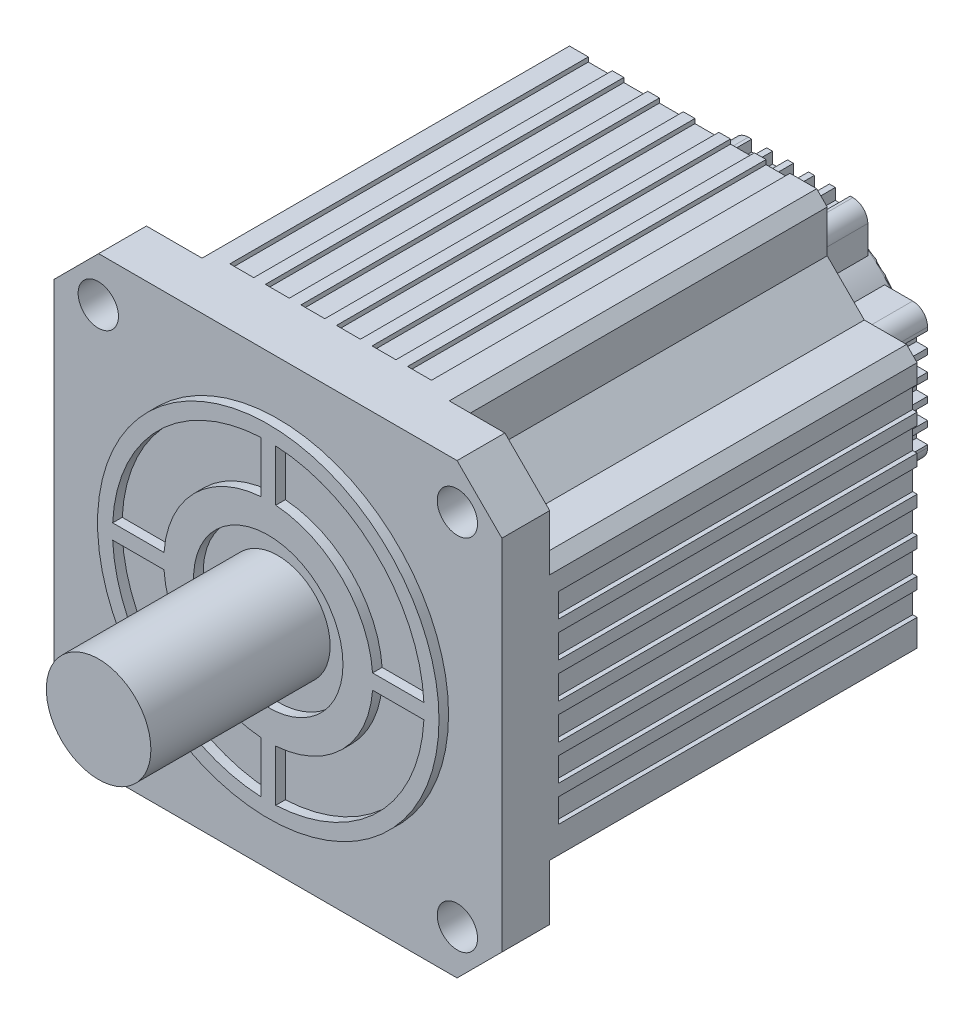
SolidWorks part; units mm, degrees
note: The reader was unsure of these and kept them because the rebuilt part matched: shared geometry of "草图16<3>".
ref_plane "前视基准面" through (0, 0, 0) normal (0, 0, 1) x (1, 0, 0)
ref_plane "上视基准面" through (0, 0, 0) normal (0, 1, 0) x (1, 0, 0)
ref_plane "右视基准面" through (0, 0, 0) normal (1, 0, 0) x (0, 0, -1)
sketch "草图1" plane through (0, 0, 0) normal (0, 0, 1) x (1, 0, 0)
  line L0 (-60, 75) -> (-75, 60)
  line L1 (-60, 75) -> (60, 75)
  line L2 (-75, 60) -> (-75, -60)
  line L3 (-60, -75) -> (60, -75)
  line L4 (75, 60) -> (75, -60)
  line L5 (-75, 75) -> (75, -75) construction
  line L6 (-75, -75) -> (75, 75) construction
  line L7 (60, 75) -> (75, 60)
  line L8 (75, -60) -> (60, -75)
  line L9 (-75, -60) -> (-60, -75)
  point P0 (0, 0)
  dimension "D1" = 150
  dimension "D2" = 150
extrude "拉伸1" add sketch "草图1" along normal blind 16
sketch "草图3" plane through (0, 0, 16) normal (0, 0, 1) x (1, 0, 0)
  line L0 (67.5, 67.5) -> (-67.5, -67.5) construction
  line L1 (75, 60) -> (60, 75) construction
  line L2 (-75, -60) -> (-60, -75) construction
  line L3 (-67.5, 67.5) -> (67.5, -67.5) construction
  line L4 (-60, 75) -> (-75, 60) construction
  line L5 (60, -75) -> (75, -60) construction
  circle A0 centre (0, 0) radius 100 construction
sketch "草图5" plane through (0, 0, 16) normal (0, 0, 1) x (1, 0, 0)
  circle A0 centre (0, 0) radius 57.15
  dimension "D1" = 114.3
extrude "拉伸2" add sketch "草图5" along normal blind 3.2
sketch "草图6" plane through (0, 0, 19.2) normal (0, 0, 1) x (1, 0, 0)
  circle A0 centre (0, 0) radius 52.15
  dimension "D1" = 104.3
extrude "拉伸3" cut sketch "草图6" against normal blind 3.2
sketch "草图7" plane through (0, 0, 16) normal (0, 0, 1) x (1, 0, 0)
  circle A0 centre (0, 0) radius 17.5
  dimension "D1" = 35
extrude "拉伸4" add sketch "草图7" along normal blind 60
sketch "草图9" plane through (0, 0, 16) normal (0, 0, 1) x (1, 0, 0)
  line L0 (0, 0) -> (102.718, 0) construction
  line L1 (25.0777, 2.5) -> (54.3657, 2.5)
  line L3 (25.0777, -2.5) -> (54.3657, -2.5)
  line L4 (54.3657, 2.5) -> (54.3657, -2.5)
  line L5 (25.0777, 2.5) -> (25.0777, -2.5)
  dimension "D1" = 2.5
  dimension "D2" = 2.5
extrude "拉伸5" add sketch "草图9" along normal blind 3.2
pattern_circular "阵列(圆周)1" count 4 over 360 about axis through (0, 0, 0) along (0, 0, 1) of "拉伸5"
sketch "草图10" plane through (0, 0, 16) normal (0, 0, 1) x (1, 0, 0)
  circle A0 centre (0, 0) radius 35
  circle A1 centre (0, 0) radius 25
extrude "拉伸6" add sketch "草图10" along normal blind 3.2
sketch "草图11" plane through (0, 0, 0) normal (0, 0, -1) x (-1, 0, 0)
  line L0 (-75, 41.3757) -> (-75, 11.8722)
  line L1 (-75, -60) -> (-75, 60) construction
  line L2 (75, 60) -> (75, -60) construction
  line L3 (11.8722, 75) -> (-41.3757, 75)
  line L4 (-60, 75) -> (60, 75) construction
  line L5 (-41.3757, 75) -> (-44.9113, 71.4645)
  line L6 (-71.4645, 44.9113) -> (-57.3223, 44.9113)
  line L7 (-57.3223, 44.9113) -> (-44.9113, 57.3223)
  line L8 (-44.9113, 57.3223) -> (-44.9113, 71.4645)
  line L9 (41.3757, 75) -> (11.8722, 75)
  line L10 (-71.4645, 44.9113) -> (-75, 41.3757)
  line L11 (44.9113, 71.4645) -> (41.3757, 75)
  line L12 (44.9113, 71.4645) -> (44.9113, 57.3223)
  line L13 (44.9113, 57.3223) -> (57.3223, 44.9113)
  line L14 (57.3223, 44.9113) -> (71.4645, 44.9113)
  line L15 (75, 41.3757) -> (71.4645, 44.9113)
  line L16 (75, -41.3757) -> (75, -11.8722)
  line L17 (71.4645, -44.9113) -> (75, -41.3757)
  line L18 (71.4645, -44.9113) -> (57.3223, -44.9113)
  line L19 (57.3223, -44.9113) -> (44.9113, -57.3223)
  line L20 (44.9113, -57.3223) -> (44.9113, -71.4645)
  line L21 (41.3757, -75) -> (44.9113, -71.4645)
  line L22 (-41.3757, -75) -> (-11.8722, -75)
  line L23 (-44.9113, -71.4645) -> (-41.3757, -75)
  line L24 (-44.9113, -71.4645) -> (-44.9113, -57.3223)
  line L25 (-44.9113, -57.3223) -> (-57.3223, -44.9113)
  line L26 (-57.3223, -44.9113) -> (-71.4645, -44.9113)
  line L29 (-75, -41.3757) -> (-71.4645, -44.9113)
  line L30 (-75, 11.8722) -> (-75, -41.3757)
  line L31 (75, 41.3757) -> (75, -11.8722)
  line L32 (-11.8722, -75) -> (41.3757, -75)
  point P2 (-75, 41.3757)
  point P7 (-71.4645, 44.9113)
  point P39 (-44.9113, 71.4645)
  point P42 (-41.3757, 75)
  dimension "D9" = 45
  dimension "D14" = 10
  dimension "D6" = 5
  dimension "D7" = 5
  dimension "D10" = 45
extrude "拉伸7" add sketch "草图11" along normal blind 123
sketch "草图12" plane through (0, 0, -123) normal (0, 0, -1) x (-1, 0, 0)
  line L0 (-42.5, -17.5) -> (-42.5, 17.5)
  line L1 (-17.5, -42.5) -> (17.5, -42.5)
  line L2 (42.5, -17.5) -> (42.5, 17.5)
  line L3 (22.5, 28.1066) -> (22.5, 37.4966)
  line L5 (-22.5, 28.1066) -> (-22.5, 37.4966)
  line L6 (-17.5, 42.4966) -> (17.5, 42.4966)
  line L10 (-28.1066, 22.5) -> (-37.5, 22.5)
  line L11 (37.5, 22.5) -> (28.1066, 22.5)
  line L12 (28.1066, -22.5) -> (37.5, -22.5)
  line L14 (22.5, -37.5) -> (22.5, -28.1066)
  line L15 (-22.5, -28.1066) -> (-22.5, -37.5)
  line L17 (-37.5, -22.5) -> (-28.1066, -22.5)
  line L23 (22.5, 28.1066) -> (22.5, 30) [skipped]
  arc A0 (-37.5, 22.5) -> (-42.5, 17.5) centre (-37.5, 17.5) ccw
  arc A1 (-17.5, 42.4966) -> (-22.5, 37.4966) centre (-17.5, 37.4966) ccw
  arc A2 (22.5, 37.4966) -> (17.5, 42.4966) centre (17.5, 37.4966) ccw
  arc A3 (42.5, 17.5) -> (37.5, 22.5) centre (37.5, 17.5) ccw
  arc A4 (37.5, -22.5) -> (42.5, -17.5) centre (37.5, -17.5) ccw
  arc A5 (17.5, -42.5) -> (22.5, -37.5) centre (17.5, -37.5) ccw
  arc A6 (-22.5, -37.5) -> (-17.5, -42.5) centre (-17.5, -37.5) ccw
  arc A7 (-42.5, -17.5) -> (-37.5, -22.5) centre (-37.5, -17.5) ccw
  arc A10 (28.1066, 22.5) -> (22.5, 28.1066) centre (0, 0) ccw
  arc A11 (22.5, -28.1066) -> (28.1066, -22.5) centre (0, 0) ccw
  arc A12 (-28.1066, -22.5) -> (-22.5, -28.1066) centre (0, 0) ccw
  arc A16 (-22.5, 28.1066) -> (-28.1066, 22.5) centre (0, 0) ccw
  point P6 (-22.5, 42.4966)
  point P11 (22.5, 42.4966)
  point P38 (-26.0355, 22.5)
  point P41 (-22.5, 26.0355)
  dimension "D1" = 5
  dimension "D2" = 14.39
  dimension "D4" = 5
  dimension "D3" = 14.39
  dimension "D8" = 5
extrude "拉伸8" add sketch "草图12" along normal blind 36
sketch "草图13" plane through (0, 0, -159) normal (0, 0, -1) x (-1, 0, 0)
  circle A0 centre (0, 0) radius 36.0032
extrude "拉伸9" add sketch "草图13" along normal blind 2
fillet "圆角5" radius 1 1 edges at (-36.0032, 0, -161)
sketch "草图14" plane through (0, 0, -123) normal (0, 0, -1) x (-1, 0, 0)
  line L0 (-32.4376, 73.5025) -> (-24.4376, 73.5025)
  line L2 (-24.4376, 73.5025) -> (-24.4376, 87.3537)
  line L3 (-24.4376, 87.3537) -> (-32.4376, 87.3537)
  line L5 (-32.4376, 87.3537) -> (-32.4376, 73.5025)
extrude "拉伸10" cut sketch "草图14" against normal blind 120
sketch "草图15" plane through (0, 0, -159) normal (0, 0, -1) x (-1, 0, 0)
  line L0 (-16.3794, -43.7336) -> (-16.3794, -38.7472)
  line L1 (-16.3794, -38.7472) -> (-11.3794, -38.7472)
  line L2 (-11.3794, -38.7472) -> (-11.3794, -43.7336)
  line L3 (-11.3794, -43.7336) -> (-16.3794, -43.7336)
  dimension "D1" = 5
extrude "拉伸11" cut sketch "草图15" against normal blind 44
pattern_linear "阵列(线性)4" count 5 spacing 7 along (-1, 0, 0) of "拉伸11"
sketch "草图16" plane through (0, 0, -161) normal (0, 0, -1) x (-1, 0, 0)
  line L0 (3.7784, 12.9251) -> (-4.4895, 12.9251)
  line L1 (-5.3556, 11.4251) -> (-2.0876, 5.7648)
  line L2 (-0.3556, 5.7648) -> (2.9124, 11.4251)
  line L3 (3.7784, 12.9251) -> (13.498, 12.9251)
  line L4 (3.7784, 13.9251) -> (13.2661, 13.9251)
  line L5 (-2.0876, 20.0854) -> (-10.3556, 5.7648)
  line L6 (-9.4895, 4.2648) -> (7.0464, 4.2648)
  line L7 (7.9124, 5.7648) -> (4.6444, 11.4251)
  line L8 (3.7784, 13.9251) -> (13.498, 13.9251) construction
  line L9 (2.9124, 14.4251) -> (-0.3556, 20.0854)
  line L10 (-6.7983, -9.8656) -> (-14.7983, -9.8656)
  line L11 (-15.7983, -10.8656) -> (-15.7983, -14.8656)
  line L12 (-14.7983, -15.8656) -> (-6.7983, -15.8656)
  line L13 (-6.7983, -15.8656) -> (-6.7983, -11.7903)
  line L14 (-6.7983, -11.7903) -> (-10.7983, -11.7903)
  line L15 (-10.7983, -11.7903) -> (-10.7983, -12.8656)
  line L16 (-10.7983, -12.8656) -> (-10.0983, -12.8656)
  line L17 (-9.7983, -13.1656) -> (-9.7983, -14.5656)
  line L18 (-10.0983, -14.8656) -> (-12.7983, -14.8656)
  line L19 (-12.7983, -14.8656) -> (-12.7983, -10.8656)
  line L20 (-12.7983, -10.8656) -> (-6.7983, -10.8656)
  line L21 (-6.7983, -10.8656) -> (-6.7983, -9.8656)
  line L22 (3.7341, -9.8656) -> (-4.2659, -9.8656)
  line L23 (-5.2659, -10.8656) -> (-5.2659, -12.8656)
  line L24 (-4.2659, -13.8656) -> (0.4341, -13.8656)
  line L25 (0.7341, -14.1656) -> (0.7341, -14.4491)
  line L26 (-5.2659, -14.7491) -> (0.4341, -14.7491)
  line L27 (-5.2659, -14.7491) -> (-5.2659, -15.8656)
  line L28 (-5.2659, -15.8656) -> (2.7341, -15.8656)
  line L29 (3.7341, -14.8656) -> (3.7341, -12.8656)
  line L30 (2.7341, -11.8656) -> (-1.9659, -11.8656)
  line L31 (-2.2659, -11.5656) -> (-2.2659, -11.1656)
  line L32 (-1.9659, -10.8656) -> (3.7341, -10.8656)
  line L33 (6.1202, -9.8656) -> (6.1202, -15.8656)
  line L34 (6.1202, -15.8656) -> (9.1202, -15.8656)
  line L35 (9.1202, -15.8656) -> (9.1202, -14.3656)
  line L36 (9.1202, -14.3656) -> (11.6916, -15.8656)
  line L37 (11.6916, -15.8656) -> (15.1202, -15.8656)
  line L38 (15.1202, -15.8656) -> (9.1202, -12.3656)
  line L39 (9.1202, -12.3656) -> (9.1202, -9.8656)
  line L40 (9.1202, -9.8656) -> (6.1202, -9.8656)
  line L41 (3.7341, -10.8656) -> (3.7341, -9.8656)
  circle A0 centre (-1.2216, 10.0383) radius 15
  arc A1 (3.7784, 13.9251) -> (2.9124, 14.4251) centre (3.7784, 14.9251) cw
  arc A2 (-0.3556, 20.0854) -> (-2.0876, 20.0854) centre (-1.2216, 19.5854) ccw
  arc A3 (-5.3556, 11.4251) -> (-4.4895, 12.9251) centre (-4.4895, 11.9251) cw
  arc A4 (-9.4895, 4.2648) -> (-10.3556, 5.7648) centre (-9.4895, 5.2648) cw
  arc A5 (7.9124, 5.7648) -> (7.0464, 4.2648) centre (7.0464, 5.2648) cw
  arc A6 (2.9124, 11.4251) -> (4.6444, 11.4251) centre (3.7784, 10.9251) cw
  arc A7 (-2.0876, 5.7648) -> (-0.3556, 5.7648) centre (-1.2216, 6.2648) ccw
  circle A8 centre (12.2447, -11.202) radius 1.5
  arc A9 (-14.7983, -15.8656) -> (-15.7983, -14.8656) centre (-14.7983, -14.8656) cw
  arc A10 (-14.7983, -9.8656) -> (-15.7983, -10.8656) centre (-14.7983, -10.8656) ccw
  arc A11 (-5.2659, -10.8656) -> (-4.2659, -9.8656) centre (-4.2659, -10.8656) cw
  arc A12 (-4.2659, -13.8656) -> (-5.2659, -12.8656) centre (-4.2659, -12.8656) cw
  arc A13 (3.7341, -12.8656) -> (2.7341, -11.8656) centre (2.7341, -12.8656) ccw
  arc A14 (2.7341, -15.8656) -> (3.7341, -14.8656) centre (2.7341, -14.8656) ccw
  arc A15 (-1.9659, -10.8656) -> (-2.2659, -11.1656) centre (-1.9659, -11.1656) ccw
  arc A16 (-1.9659, -11.8656) -> (-2.2659, -11.5656) centre (-1.9659, -11.5656) cw
  arc A17 (0.7341, -14.1656) -> (0.4341, -13.8656) centre (0.4341, -14.1656) ccw
  arc A18 (0.4341, -14.7491) -> (0.7341, -14.4491) centre (0.4341, -14.4491) ccw
  arc A19 (-9.7983, -13.1656) -> (-10.0983, -12.8656) centre (-10.0983, -13.1656) ccw
  arc A20 (-9.7983, -14.5656) -> (-10.0983, -14.8656) centre (-10.0983, -14.5656) cw
  point P3 (-1.2216, 10.0383)
  point P16 (3.2011, 13.9251)
  point P88 (-9.7983, -12.8656)
  point P91 (-9.7983, -14.8656)
  dimension "D1" = 30
  dimension "D3" = 1
  dimension "D29" = 3
  dimension "D31" = 1
  dimension "D32" = 1
  dimension "D33" = 0.3
  dimension "D2" = 1
  dimension "D4" = 6
  dimension "D5" = 6
  dimension "D6" = 1
  dimension "D7" = 6
  dimension "D8" = 9
  dimension "D9" = 9
  dimension "D10" = 9
  dimension "D11" = 3
  dimension "D12" = 1
  dimension "D13" = 3
  dimension "D14" = 1
  dimension "D15" = 1
  dimension "D16" = 3
  dimension "D17" = 3
  dimension "D18" = 2
  dimension "D19" = 3
  dimension "D20" = 9
  dimension "D21" = 1.5
  dimension "D22" = 3
  dimension "D23" = 2
  dimension "D24" = 1
  dimension "D26" = 6
  dimension "D30" = 2
extrude "拉伸12" add sketch "草图16" along normal blind 2 contours L1 A7 L2 A6 L7 A5 L6 A4 L5 A2 L9 A1 L4 A0 L3 L0 A3
extrude "拉伸13" add sketch "草图16<3>" along normal blind 2 contours L17 A20 L18 L19 L20 L21 L10 A10 L11 A9 L12 L13 L14 L15 L16 A19 | A18 L26 L27 L28 A14 L29 A13 L30 A16 L31 A15 L32 L41 L22 A11 L23 A12 L24 A17 L25 | L33 L34 L35 L36 L37 L38 L39 L40 | A8
sketch "草图16<3>" plane through (0, 0, -161) normal (0, 0, -1) x (-1, 0, 0) same geometry as "草图16"
pattern_linear "阵列(线性)3" count 6 spacing 11.9 along (-1, 0, 0) of "拉伸10"
pattern_circular "阵列(圆周)2" count 4 over 360 about axis through (0, 0, 0) along (0, 0, 1) of "阵列(线性)3", "拉伸10"
pattern_circular "阵列(圆周)3" count 4 every 90 about axis through (0, 0, 0) along (0, 0, 1) of "拉伸11", "阵列(线性)4"
sketch "草图17" plane through (0, 0, 16) normal (0, 0, 1) x (1, 0, 0)
  line L0 (-67.5, 67.5) -> (67.5, -67.5) construction
  line L1 (-60, 75) -> (-75, 60) construction
  line L2 (60, -75) -> (75, -60) construction
  line L3 (67.5, -67.5) -> (-67.5, -67.5) construction
  line L4 (-75, -60) -> (-60, -75) construction
  line L5 (-67.5, -67.5) -> (67.5, 67.5) construction
  line L6 (75, 60) -> (60, 75) construction
  circle A0 centre (0, 0) radius 85 construction
  circle A1 centre (-60.1041, 60.1041) radius 6.75
  circle A2 centre (60.1041, 60.1041) radius 6.75
  circle A3 centre (60.1041, -60.1041) radius 6.75
  circle A4 centre (-60.1041, -60.1041) radius 6.75
  dimension "D1" = 170
  dimension "D2" = 13.5
  dimension "D3" = 13.5
  dimension "D4" = 13.5
  dimension "D5" = 13.5
extrude "拉伸15" cut sketch "草图17" against normal blind 30
